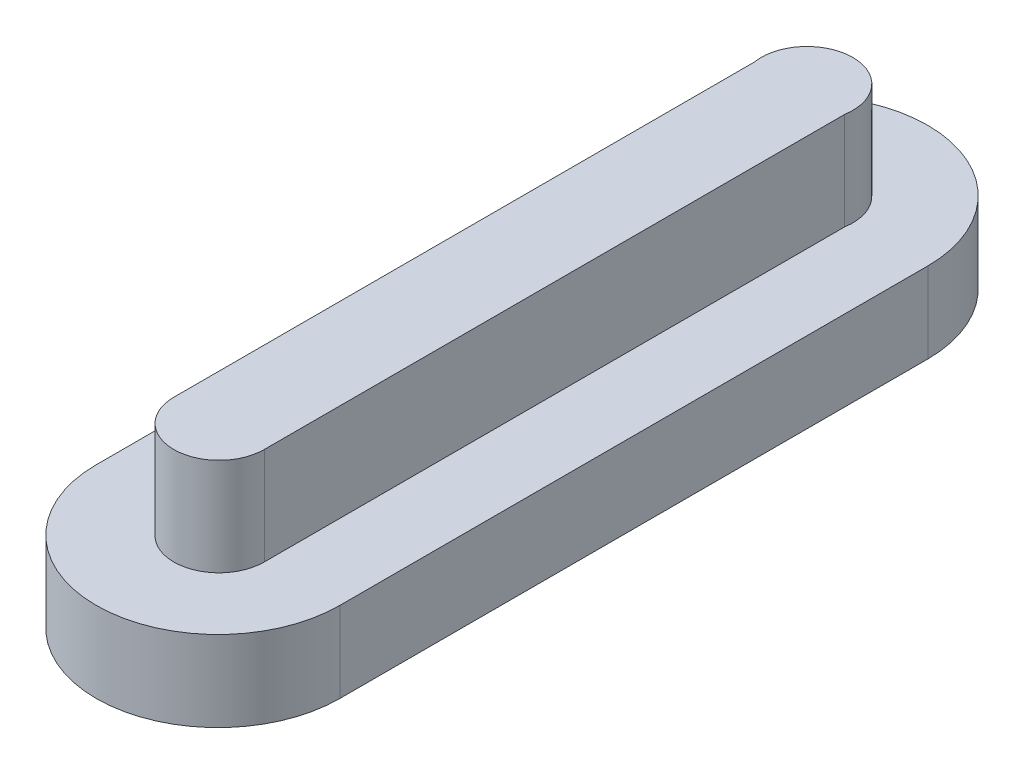
SolidWorks part; units mm, degrees
ref_plane "Front" through (0, 0, 0) normal (0, 0, 1) x (1, 0, 0)
ref_plane "Top" through (0, 0, 0) normal (0, 1, 0) x (1, 0, 0)
ref_plane "Right" through (0, 0, 0) normal (1, 0, 0) x (0, 0, -1)
sketch "Sketch1" plane through (0, 0, 0) normal (0, 1, 0) x (1, 0, 0)
  line L0 (0, 0) -> (0, -35) construction
  line L1 (7.25, 0) -> (7.25, -35)
  line L2 (-7.25, 0) -> (-7.25, -35)
  arc A0 (7.25, 0) -> (-7.25, 0) centre (0, 0) ccw
  arc A1 (-7.25, -35) -> (7.25, -35) centre (0, -35) ccw
  point P3 (0, -17.5)
extrude "Boss-Extrude1" add sketch "Sketch1" along normal blind 4.8
sketch "Sketch3" plane through (0, 4.8, 0) normal (0, 1, 0) x (1, 0, 0)
  line L1 (-2.6226, -0.0113) -> (2.7638, -0.0113)
  line L2 (-2.6226, -0.0113) -> (-2.6226, -35.0113)
  line L3 (-2.6226, -35.0113) -> (2.7638, -35.0113)
  line L4 (2.7638, -0.0113) -> (2.7638, -35.0113)
  circle A0 centre (0.0706, -0.0113) radius 2.7299
  circle A1 centre (0.0706, -35.0113) radius 2.6932
  dimension "D1" = 35
extrude "Boss-Extrude2" add sketch "Sketch3" along normal blind 5.8 contours L4 A0 L2 L1 | A1 L4 A0 L2 | L3 A1 | L3 A1 | L2 A0 L4 L1 region at (0.0706, 4.8, -1.1448) region at (0.0706, 4.8, 1.1718) region at (0.0706, 4.8, 17.5388) region at (0.0706, 4.8, 33.8683) region at (0.0706, 4.8, 36.1543)
sketch "Sketch4" plane through (0, 10.6, 0) normal (0, 1, 0) x (1, 0, 0)
  line L0 (0, 0) -> (0.0706, -35.0113) construction
  line L1 (7.2531, 0.0146) -> (7.3237, -34.9967)
  line L2 (-7.2531, -0.0146) -> (-7.1825, -35.0259)
  arc A0 (7.2531, 0.0146) -> (-7.2531, -0.0146) centre (0, 0) ccw
  arc A1 (-7.1825, -35.0259) -> (7.3237, -34.9967) centre (0.0706, -35.0113) ccw
  point P4 (0.0353, -17.5056)
extrude "Boss-Extrude3" add sketch "Sketch4" along normal blind 8.1
sketch "Sketch6" plane through (0, 18.7, 0) normal (0, 1, 0) x (1, 0, 0)
  line L1 (4.4439, 25.9416) -> (-24.5798, 25.9416)
  line L2 (4.4439, 25.9416) -> (4.4439, -52.1157)
  line L3 (4.4439, -52.1157) -> (-24.5798, -52.1157)
  line L4 (-24.5798, 25.9416) -> (-24.5798, -52.1157)
  line L5 (-24.5798, 36.4587) -> (23.3831, 36.4587)
  line L6 (-24.5798, 36.4587) -> (-24.5798, -65.8474)
  line L7 (-24.5798, -65.8474) -> (23.3831, -65.8474)
  line L8 (23.3831, 36.4587) -> (23.3831, -65.8474)
  arc M5 (7.2531, 0.0146) -> (-7.2531, -0.0146) centre (0, 0) ccw
  line M6 (-7.2531, -0.0146) -> (-7.1825, -35.0259)
  arc M7 (-7.1825, -35.0259) -> (7.3237, -34.9967) centre (0.0706, -35.0113) ccw
  line M8 (7.3237, -34.9967) -> (7.2531, 0.0146)
extrude "Cut-Extrude2" cut sketch "Sketch6" against normal blind 8.1 contours L8 L5 L6 L1 L2 L3 L7 M5 M8 M7 | L1 L4 L3 L2 M7 M6 M5 | L2 M5 M6 M7 | L2 M5 M7 M8 region at (-12.8995, 18.7, 11.6771) region at (7.6067, 18.7, 15.9971) region at (5.8171, 18.7, 17.6322) region at (-1.2505, 18.7, 17.4775)
